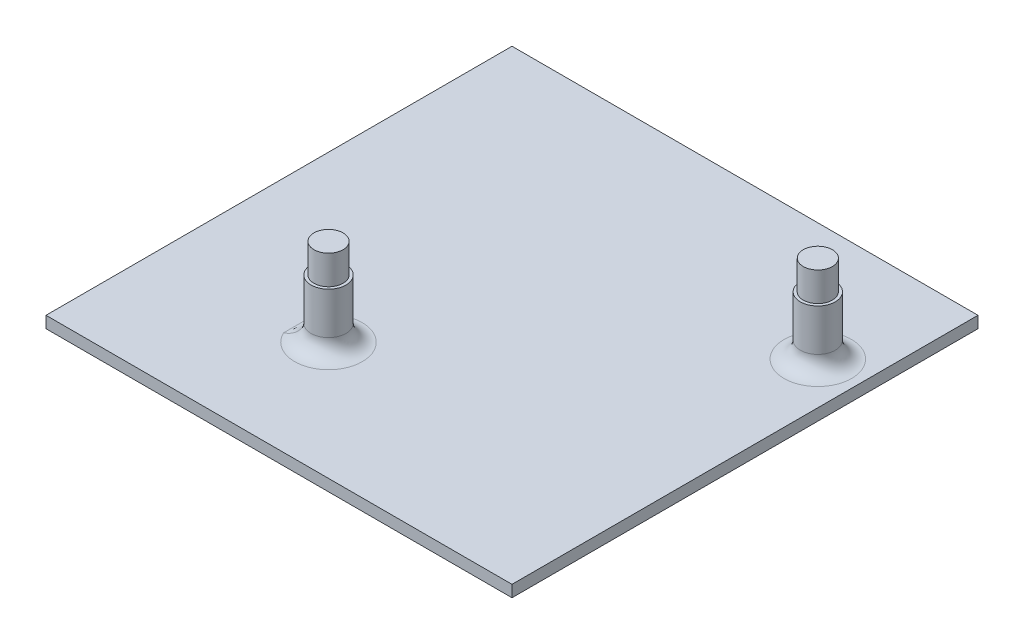
SolidWorks part; units mm, degrees
ref_plane "Front Plane" through (0, 0, 0) normal (0, 0, 1) x (1, 0, 0)
ref_plane "Top Plane" through (0, 0, 0) normal (0, 1, 0) x (1, 0, 0)
ref_plane "Right Plane" through (0, 0, 0) normal (1, 0, 0) x (0, 0, -1)
sketch "Sketch1" plane through (0, 0, 0) normal (0, 1, 0) x (1, 0, 0)
  line L0 (-27.5, 27.5) -> (-27.5, 40)
  line L1 (-27.5, 27.5) -> (27.5, 27.5)
  line L2 (-27.5, 27.5) -> (-27.5, -27.5)
  line L3 (-27.5, -27.5) -> (27.5, -27.5)
  line L4 (27.5, 27.5) -> (27.5, -27.5)
  line L5 (-27.5, 27.5) -> (27.5, -27.5) construction
  line L6 (-27.5, -27.5) -> (27.5, 27.5) construction
  line L7 (-27.5, 40) -> (52.5, 40)
  line L8 (-27.5, -27.5) -> (-27.5, -40)
  line L9 (-27.5, -40) -> (52.5, -40)
  line L10 (52.5, 40) -> (52.5, -40)
  line L11 (-27.5, -40) -> (-27.5, -27.5)
  circle A0 centre (22.25, -19.75) radius 2.5 construction
  circle A1 centre (-22.25, 22.25) radius 2.5 construction
  point P0 (0, 0)
  point P14 (52.5, 0)
  dimension "D5" = 5
  dimension "D1" = 55
  dimension "D2" = 5.25
  dimension "D3" = 19.75
  dimension "D4" = 5.25
  dimension "D6" = 80
  dimension "D7" = 80
extrude "Boss-Extrude1" add sketch "Sketch1" along normal blind 2 contours L10 L7 L0 L1 L4 L3 L8 L9 | L4 L1 L2 L3 region at (-26.3686, 0, -33.75) region at (0, 0, 0)
sketch "Sketch2" plane through (0, 2, 0) normal (0, 1, 0) x (1, 0, 0)
  line L0 (-22.25, -19.75) -> (-22.25, -40) construction
  line L1 (-27.5, -40) -> (52.5, -40) construction
  line L2 (22.25, 19.75) -> (22.25, 40) construction
  line L3 (-27.5, 40) -> (52.5, 40) construction
  circle A0 centre (-22.25, -19.75) radius 3
  circle A1 centre (22.25, 19.75) radius 3
  dimension "D5" = 6
  dimension "D6" = 6
  dimension "D3" = 22.25
  dimension "D4" = 22.25
  dimension "D7" = 39.5
extrude "Boss-Extrude2" add sketch "Sketch2" along normal blind 10
fillet "Fillet1" radius 2.8 2 edges at (22.25, 2, -16.75) (-22.25, 2, 22.75)
sketch "Sketch3" plane through (0, 12, 0) normal (0, 1, 0) x (1, 0, 0)
  circle A0 centre (-22.25, -19.75) radius 2.5
  circle A1 centre (22.25, 19.75) radius 2.5
  dimension "D1" = 5
extrude "Boss-Extrude3" add sketch "Sketch3" along normal blind 5
sketch "Sketch4" plane through (0, 2, 0) normal (0, 1, 0) x (1, 0, 0)
  line L0 (-27.5, -40) -> (52.5, -40) construction
  line L1 (52.5, 40) -> (29.5, 40)
  line L2 (52.5, 40) -> (52.5, -40)
  line L3 (52.5, -40) -> (29.5, -40)
  line L4 (29.5, 40) -> (29.5, -40)
  dimension "D1" = 23
extrude "Cut-Extrude1" cut sketch "Sketch4" against normal through all
sketch "Sketch5" plane through (0, 2, 0) normal (0, 1, 0) x (1, 0, 0)
  line L1 (-27.5, 40) -> (-50.5, 40)
  line L2 (-27.5, 40) -> (-27.5, -40)
  line L3 (-27.5, -40) -> (-50.5, -40)
  line L4 (-50.5, 40) -> (-50.5, -40)
  dimension "D1" = 23
extrude "Boss-Extrude4" add sketch "Sketch5" against normal up to surface (2 mm away) up to face at (1, 0, 0)
equation "\"d\" = 23"
equation "\"D1@Sketch4\"=\"d\""
equation "\"D1@Sketch5\"=\"d\""
